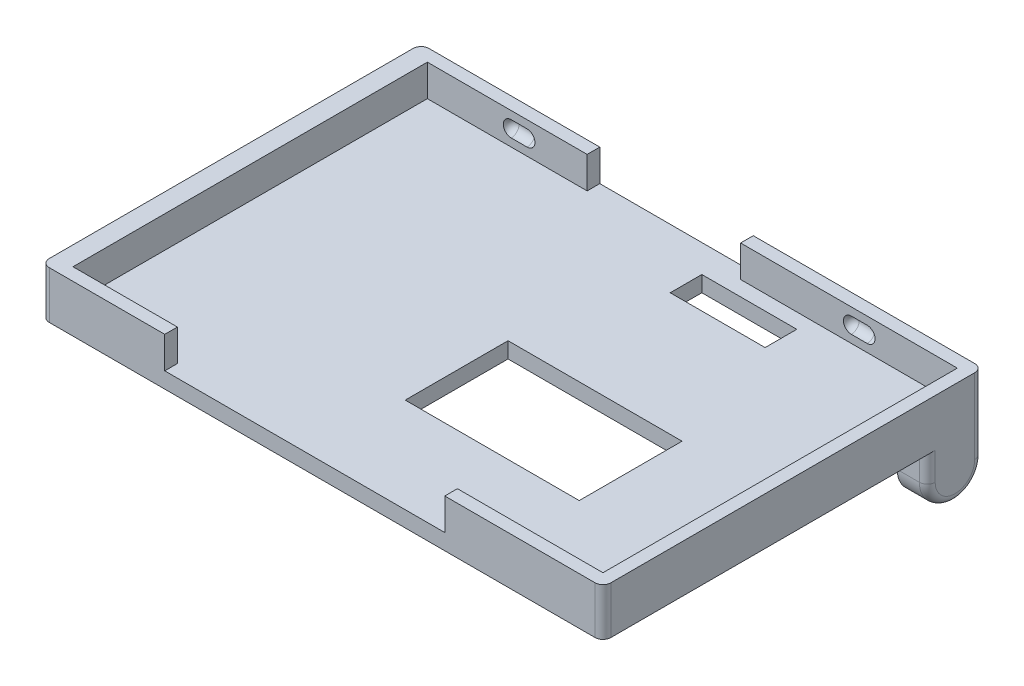
SolidWorks part; units mm, degrees
ref_plane "前视基准面" through (0, 0, 0) normal (0, 0, 1) x (1, 0, 0)
ref_plane "上视基准面" through (0, 0, 0) normal (0, 1, 0) x (1, 0, 0)
ref_plane "右视基准面" through (0, 0, 0) normal (1, 0, 0) x (0, 0, -1)
sketch "草图1" plane through (0, 0, 0) normal (0, 1, 0) x (1, 0, 0)
  line L1 (-17.75, 12) -> (17.75, 12)
  line L2 (-17.75, 12) -> (-17.75, -12)
  line L3 (-17.75, -12) -> (17.75, -12)
  line L4 (17.75, 12) -> (17.75, -12)
  line L5 (-17.75, 12) -> (17.75, -12) construction
  line L6 (-17.75, -12) -> (17.75, 12) construction
  point P0 (0, 0)
  dimension "D1" = 24
  dimension "D2" = 35.5
extrude "凸台-拉伸1" add sketch "草图1" along normal blind 3
sketch "草图2" plane through (0, 3, 0) normal (0, 1, 0) x (1, 0, 0)
  line L0 (17.75, 12) -> (-17.75, 12) construction
  line L1 (-15.75, 10) -> (15.75, 10)
  line L2 (-15.75, 10) -> (-15.75, -10)
  line L3 (-15.75, -10) -> (15.75, -10)
  line L4 (15.75, 10) -> (15.75, -10)
  line L5 (-15.75, 10) -> (15.75, -10) construction
  line L6 (-15.75, -10) -> (15.75, 10) construction
  line L7 (-17.75, 12) -> (-17.75, -12) construction
  point P0 (0, 0)
  dimension "D1" = 2
  dimension "D2" = 2
extrude "切除-拉伸1" cut sketch "草图2" against normal blind 2
sketch "草图4" plane through (0, 0, 0) normal (0, -1, 0) x (1, 0, 0)
  line L1 (-17.75, -12) -> (-15.85, -12)
  line L2 (-17.75, -12) -> (-17.75, -8.5)
  line L3 (-17.75, -8.5) -> (-15.85, -8.5)
  line L4 (-15.85, -12) -> (-15.85, -8.5)
  line L5 (17.75, -12) -> (15.85, -12)
  line L6 (17.75, -12) -> (17.75, -8.5)
  line L7 (17.75, -8.5) -> (15.85, -8.5)
  line L8 (15.85, -12) -> (15.85, -8.5)
  dimension "D1" = 3.5
  dimension "D2" = 1.9
  dimension "D3" = 1.9
  dimension "D4" = 3.5
extrude "凸台-拉伸2" add sketch "草图4" along normal blind 3.5
sketch "草图5" plane through (-17.75, 0, 0) normal (-1, 0, 0) x (0, 0, 1)
  line L1 (-12, 3) -> (-12, -3.5) construction
  line L2 (-12, -1.75) -> (-12, -3.5)
  line L5 (-10.25, -3.5) -> (-12, -3.5)
  arc A1 (-12, -1.75) -> (-10.25, -3.5) centre (-10.25, -1.75) ccw
  dimension "D1" = 1.75
extrude "切除-拉伸3" cut sketch "草图5" against normal blind 2
sketch "草图6" plane through (-17.75, 0, 0) normal (-1, 0, 0) x (0, 0, 1)
  line L0 (-8.5, -3.5) -> (-10.25, -3.5)
  line L1 (-8.5, -3.5) -> (-10.25, -3.5) construction
  line L2 (-8.5, -3.5) -> (-8.5, 0) construction
  line L3 (-8.5, -3.5) -> (-8.5, -1.75)
  arc A0 (-12, -1.75) -> (-10.25, -3.5) centre (-10.25, -1.75) ccw construction
  arc A1 (-10.25, -3.5) -> (-8.5, -1.75) centre (-10.25, -1.75) ccw
extrude "切除-拉伸4" cut sketch "草图6" against normal blind 2
sketch "草图7" plane through (17.75, 0, 0) normal (1, 0, 0) x (0, 0, -1)
  line L0 (8.5, -3.5) -> (10.25, -3.5)
  line L1 (12, -3.5) -> (8.5, -3.5) construction
  line L2 (8.5, -3.5) -> (8.5, 0) construction
  line L3 (8.5, -1.75) -> (8.5, -3.5)
  arc A0 (10.25, -3.5) -> (8.5, -1.75) centre (10.25, -1.75) cw
extrude "切除-拉伸5" cut sketch "草图7" against normal blind 2
sketch "草图8" plane through (17.75, 0, 0) normal (1, 0, 0) x (0, 0, -1)
  line L0 (12, -3.5) -> (10.25, -3.5)
  line L1 (12, 3) -> (12, -3.5) construction
  line L2 (12, -1.75) -> (12, -3.5)
  arc A0 (10.25, -3.5) -> (12, -1.75) centre (10.25, -1.75) ccw
extrude "切除-拉伸6" cut sketch "草图8" against normal blind 2
sketch "草图10" plane through (15.85, 0, 0) normal (-1, 0, 0) x (0, 0, 1)
  line L0 (-8.5, -1.75) -> (-8.5, 0) construction
  line L1 (12, 0) -> (-8.5, 0) construction
  circle A0 centre (-10.25, -1.75) radius 0.6
  dimension "D1" = 1.2
  dimension "D2" = 1.75
  dimension "D3" = 1.75
extrude "切除-拉伸8" cut sketch "草图10" against normal blind 1.5
sketch "草图11" plane through (0, 0, 0) normal (0, -1, 0) x (1, 0, 0)
  line L0 (17.75, 12) -> (17.75, -8.5) construction
  line L1 (1.75, -8.25) -> (7.75, -8.25)
  line L2 (1.75, -8.25) -> (1.75, -10.25)
  line L3 (1.75, -10.25) -> (7.75, -10.25)
  line L4 (7.75, -8.25) -> (7.75, -10.25)
  line L6 (15.85, -12) -> (-15.85, -12) construction
  dimension "D1" = 10
  dimension "D2" = 6
  dimension "D3" = 2
  dimension "D4" = 1.75
extrude "切除-拉伸9" cut sketch "草图11" against normal blind 2
sketch "草图12" plane through (-15.85, 0, 0) normal (1, 0, 0) x (0, 0, -1)
  line L0 (12, -1.75) -> (12, 0) construction
  line L1 (12, 0) -> (8.5, 0) construction
  circle A0 centre (10.25, -1.75) radius 0.6
  dimension "D1" = 1.2
  dimension "D2" = 1.75
  dimension "D3" = 1.75
extrude "切除-拉伸10" cut sketch "草图12" against normal blind 1.5
sketch "草图13" plane through (0, 3, 0) normal (0, 1, 0) x (1, 0, 0)
  line L1 (-15.6782, 11.2) -> (16.95, 11.2)
  line L2 (16.95, 11.2) -> (16.95, -11.2)
  line L3 (16.95, -11.2) -> (-15.75, -11.2)
  line L7 (17.75, 12) -> (-17.75, 12) construction
  line L10 (17.75, -12) -> (17.75, 12) construction
  line L11 (-17.75, -12) -> (17.75, -12) construction
  line L12 (-15.6782, 11.2) -> (-16.55, 11.2)
  line L13 (-16.55, 11.2) -> (-16.55, -11.2)
  line L14 (-16.55, -11.2) -> (-15.75, -11.2)
  line L15 (-17.75, 12) -> (-17.75, -12) construction
  dimension "D1" = 1.2
  dimension "D2" = 0.8
  dimension "D3" = 0.8
  dimension "D4" = 0.8
extrude "切除-拉伸11" cut sketch "草图13" against normal blind 2
sketch "草图14" plane through (0, 0, -11.2) normal (0, 0, 1) x (1, 0, 0)
  line L0 (16.95, 3) -> (-16.55, 3) construction
  line L1 (-11.25, 2.5) -> (-10.25, 2.5)
  line L2 (10.25, 2.5) -> (11.25, 2.5)
  line L3 (-11.75, 2) -> (-9.75, 2)
  line L4 (17.75, 3) -> (17.75, -1.75) construction
  line L5 (9.75, 2) -> (11.75, 2)
  line L6 (-17.75, 3) -> (-17.75, -1.75) construction
  arc A0 (-11.25, 2.5) -> (-11.75, 2) centre (-11.25, 2) ccw
  arc A2 (-10.25, 2.5) -> (-9.75, 2) centre (-10.25, 2) cw
  arc A4 (10.25, 2.5) -> (9.75, 2) centre (10.25, 2) ccw
  arc A5 (11.25, 2.5) -> (11.75, 2) centre (11.25, 2) cw
  point P4 (-10.75, 2.5)
  point P5 (-10.75, 2)
  point P14 (10.75, 2.5)
  point P15 (10.75, 2)
  dimension "D1" = 1
  dimension "D4" = 2
  dimension "D7" = 1
  dimension "D6" = 1
  dimension "D2" = 2
  dimension "D3" = 0.5
  dimension "D5" = 1
  dimension "D8" = 0.5
  dimension "D9" = 6
  dimension "D10" = 6
revolve "切除-旋转1" cut sketch "草图14" angle 360 about L5
sketch "草图15" plane through (0, 0, 11.2) normal (0, 0, -1) x (-1, 0, 0)
  line L0 (10.75, 2) -> (12.75, 2)
  line L1 (16.55, 1) -> (-16.95, 1) construction
  line L3 (-12.75, 2) -> (-10.75, 2)
  line L4 (-12.25, 2.5) -> (-11.25, 2.5)
  line L7 (-17.75, 3) -> (-17.75, 0) construction
  line L8 (11.25, 2.5) -> (12.25, 2.5)
  line L10 (17.75, 3) -> (17.75, 0) construction
  arc A4 (-12.25, 2.5) -> (-12.75, 2) centre (-12.25, 2) ccw
  arc A5 (-11.25, 2.5) -> (-10.75, 2) centre (-11.25, 2) cw
  arc A6 (11.25, 2.5) -> (10.75, 2) centre (11.25, 2) ccw
  arc A7 (12.25, 2.5) -> (12.75, 2) centre (12.25, 2) cw
  point P6 (-11.75, 2.5)
  point P9 (-11.75, 2)
  point P16 (11.75, 2.5)
  point P17 (11.75, 2)
  dimension "D1" = 2
  dimension "D2" = 1
  dimension "D6" = 5
  dimension "D3" = 1
  dimension "D4" = 0.5
  dimension "D5" = 2
  dimension "D7" = 1
  dimension "D8" = 5
revolve "切除-旋转2" cut sketch "草图15" angle 360 about L3
sketch "草图17" plane through (0, 3, 0) normal (0, 1, 0) x (1, 0, 0)
  line L0 (17.75, 12) -> (-17.75, 12) construction
  line L1 (16.95, 11.2) -> (-16.55, 11.2) construction
  line L2 (-6.45, 12) -> (3.25, 12)
  line L3 (-6.45, 12) -> (-6.45, 11.2)
  line L4 (-6.45, 11.2) -> (3.25, 11.2)
  line L5 (3.25, 12) -> (3.25, 11.2)
  line L6 (-17.75, 12) -> (-17.75, -12) construction
  line L7 (17.75, -12) -> (17.75, 12) construction
  dimension "D1" = 11.3
  dimension "D2" = 14.5
extrude "切除-拉伸12" cut sketch "草图17" against normal blind 2
sketch "草图18" plane through (0, 3, 0) normal (0, 1, 0) x (1, 0, 0)
  line L0 (-16.55, -11.2) -> (16.95, -11.2) construction
  line L1 (-9.95, -11.2) -> (7.75, -11.2)
  line L2 (-9.95, -11.2) -> (-9.95, -12)
  line L3 (-9.95, -12) -> (7.75, -12)
  line L4 (7.75, -11.2) -> (7.75, -12)
  line L5 (-17.75, -12) -> (17.75, -12) construction
  line L6 (-17.75, 12) -> (-17.75, -12) construction
  line L7 (17.75, -12) -> (17.75, 12) construction
  dimension "D1" = 7.8
  dimension "D2" = 10
extrude "切除-拉伸13" cut sketch "草图18" against normal blind 2
sketch "草图19" plane through (0, 0, 0) normal (0, -1, 0) x (1, 0, 0)
  line L0 (17.75, 12) -> (17.75, -8.5) construction
  line L1 (-0.75, 6) -> (10.25, 6)
  line L2 (-0.75, 6) -> (-0.75, -0.5)
  line L3 (-0.75, -0.5) -> (10.25, -0.5)
  line L4 (10.25, 6) -> (10.25, -0.5)
  line L5 (-17.75, 12) -> (17.75, 12) construction
  dimension "D1" = 6.5
  dimension "D2" = 11
  dimension "D3" = 7.5
  dimension "D4" = 6
extrude "切除-拉伸14" cut sketch "草图19" against normal blind 1
fillet "圆角1" radius 0.5 8 edges at (17.75, -0.875, -8.5) (17.75, -3.5, -10.25) (-17.75, -0.875, -8.5) (-17.75, -3.5, -10.25) (17.75, 1.5, 12) (17.75, 0.625, -12) (-17.75, 0.625, -12) (-17.75, 1.5, 12)
sketch "草图22" plane through (-15.85, 0, 0) normal (1, 0, 0) x (0, 0, -1)
  circle A1 centre (10.25, -1.75) radius 1.5
  dimension "D1" = 3
extrude "凸台-拉伸10" add sketch "草图22" along normal blind 0.2
sketch "草图23" plane through (-15.65, 0, 0) normal (1, 0, 0) x (0, 0, -1)
  circle A0 centre (10.25, -1.75) radius 0.6
  dimension "D1" = 1.2
extrude "切除-拉伸15" cut sketch "草图23" against normal blind 0.2
sketch "草图24" plane through (-15.65, 0, 0) normal (1, 0, 0) x (0, 0, -1)
  line L0 (10.25, -2.35) -> (10.25, -3.25)
  line L1 (10.0204, -2.3043) -> (9.676, -3.1358)
  line L2 (9.8257, -2.1743) -> (9.1893, -2.8107)
  line L3 (9.6957, -1.9796) -> (8.8642, -2.324)
  line L4 (9.65, -1.75) -> (8.75, -1.75)
  line L5 (9.6957, -1.5204) -> (8.8642, -1.176)
  line L6 (9.8257, -1.3257) -> (9.1893, -0.6893)
  line L7 (10.0204, -1.1957) -> (9.676, -0.3642)
  line L8 (10.25, -1.15) -> (10.25, -0.25)
  line L9 (10.4796, -1.1957) -> (10.824, -0.3642)
  line L10 (10.6743, -1.3257) -> (11.3107, -0.6893)
  line L11 (10.8043, -1.5204) -> (11.6358, -1.176)
  line L12 (10.85, -1.75) -> (11.75, -1.75)
  line L13 (10.8043, -1.9796) -> (11.6358, -2.324)
  line L14 (10.6743, -2.1743) -> (11.3107, -2.8107)
  line L15 (10.4796, -2.3043) -> (10.824, -3.1358)
  circle A0 centre (10.25, -1.75) radius 0.6 construction
  circle A1 centre (10.25, -1.75) radius 0.6 construction
  circle A2 centre (10.25, -1.75) radius 1.5 construction
  arc A3 (9.676, -3.1358) -> (10.25, -3.25) centre (10.25, -1.75) ccw
  arc A4 (10.824, -3.1358) -> (11.3107, -2.8107) centre (10.25, -1.75) ccw
  arc A5 (11.75, -1.75) -> (11.6358, -2.324) centre (10.25, -1.75) cw
  arc A6 (11.3107, -0.6893) -> (11.6358, -1.176) centre (10.25, -1.75) cw
  arc A7 (10.25, -0.25) -> (10.824, -0.3642) centre (10.25, -1.75) cw
  arc A8 (9.676, -0.3642) -> (9.1893, -0.6893) centre (10.25, -1.75) ccw
  arc A9 (8.8642, -1.176) -> (8.75, -1.75) centre (10.25, -1.75) ccw
  arc A10 (8.8642, -2.324) -> (9.1893, -2.8107) centre (10.25, -1.75) ccw
  arc A11 (9.6957, -1.9796) -> (9.8257, -2.1743) centre (10.25, -1.75) ccw
  arc A12 (10.0204, -2.3043) -> (10.25, -2.35) centre (10.25, -1.75) ccw
  arc A13 (10.4796, -2.3043) -> (10.6743, -2.1743) centre (10.25, -1.75) ccw
  arc A14 (10.8043, -1.9796) -> (10.85, -1.75) centre (10.25, -1.75) ccw
  arc A15 (10.8043, -1.5204) -> (10.6743, -1.3257) centre (10.25, -1.75) ccw
  arc A16 (10.4796, -1.1957) -> (10.25, -1.15) centre (10.25, -1.75) ccw
  arc A17 (10.0204, -1.1957) -> (9.8257, -1.3257) centre (10.25, -1.75) ccw
  arc A18 (9.6957, -1.5204) -> (9.65, -1.75) centre (10.25, -1.75) ccw
  point P42 (10.25, -1.75)
  dimension "D1" = 16
extrude "切除-拉伸16" cut sketch "草图24" against normal blind 0.2
fillet "圆角2" radius 0.1 16 edges at (-15.65, -2.1518, -9.2799) (-15.65, -1.75, -9.2) (-15.65, -1.3482, -9.2799) (-15.65, -1.0075, -9.5075) (-15.65, -0.7799, -9.8482) (-15.65, -0.7, -10.25) (-15.65, -0.7799, -10.6518) (-15.65, -1.0075, -10.9925) (-15.65, -1.3482, -11.2201) (-15.65, -1.75, -11.3) (-15.65, -2.1518, -11.2201) (-15.65, -2.4925, -10.9925) (-15.65, -2.7201, -10.6518) (-15.65, -2.8, -10.25) (-15.65, -2.4925, -9.5075) (-15.65, -2.7201, -9.8482)
sketch "草图25" plane through (15.85, 0, 0) normal (-1, 0, 0) x (0, 0, 1)
  circle A0 centre (-10.25, -1.75) radius 1.5
  dimension "D1" = 3
extrude "凸台-拉伸11" add sketch "草图25" along normal blind 0.2
sketch "草图26" plane through (15.65, 0, 0) normal (-1, 0, 0) x (0, 0, 1)
  circle A0 centre (-10.25, -1.75) radius 0.6
  dimension "D1" = 1.2
extrude "切除-拉伸17" cut sketch "草图26" against normal blind 0.2
sketch "草图27" plane through (15.65, 0, 0) normal (-1, 0, 0) x (0, 0, 1)
  line L0 (-10.25, -2.35) -> (-10.25, -3.25)
  line L1 (-10.4796, -2.3043) -> (-10.824, -3.1358)
  line L2 (-10.6743, -2.1743) -> (-11.3107, -2.8107)
  line L3 (-10.8043, -1.9796) -> (-11.6358, -2.324)
  line L4 (-10.85, -1.75) -> (-11.75, -1.75)
  line L5 (-10.8043, -1.5204) -> (-11.6358, -1.176)
  line L6 (-10.6743, -1.3257) -> (-11.3107, -0.6893)
  line L7 (-10.4796, -1.1957) -> (-10.824, -0.3642)
  line L8 (-10.25, -1.15) -> (-10.25, -0.25)
  line L9 (-10.0204, -1.1957) -> (-9.676, -0.3642)
  line L10 (-9.8257, -1.3257) -> (-9.1893, -0.6893)
  line L11 (-9.6957, -1.5204) -> (-8.8642, -1.176)
  line L12 (-9.65, -1.75) -> (-8.75, -1.75)
  line L13 (-9.6957, -1.9796) -> (-8.8642, -2.324)
  line L14 (-9.8257, -2.1743) -> (-9.1893, -2.8107)
  line L15 (-10.0204, -2.3043) -> (-9.676, -3.1358)
  circle A0 centre (-10.25, -1.75) radius 0.6 construction
  circle A1 centre (-10.25, -1.75) radius 1.5 construction
  arc A2 (-10.25, -0.25) -> (-10.824, -0.3642) centre (-10.25, -1.75) ccw
  arc A3 (-11.3107, -0.6893) -> (-11.6358, -1.176) centre (-10.25, -1.75) ccw
  arc A4 (-11.75, -1.75) -> (-11.6358, -2.324) centre (-10.25, -1.75) ccw
  arc A5 (-11.3107, -2.8107) -> (-10.824, -3.1358) centre (-10.25, -1.75) ccw
  arc A6 (-10.25, -3.25) -> (-9.676, -3.1358) centre (-10.25, -1.75) ccw
  arc A7 (-9.1893, -2.8107) -> (-8.8642, -2.324) centre (-10.25, -1.75) ccw
  arc A8 (-8.75, -1.75) -> (-8.8642, -1.176) centre (-10.25, -1.75) ccw
  arc A9 (-9.1893, -0.6893) -> (-9.676, -0.3642) centre (-10.25, -1.75) ccw
  arc A10 (-10.25, -1.15) -> (-10.4796, -1.1957) centre (-10.25, -1.75) ccw
  arc A11 (-10.6743, -1.3257) -> (-10.8043, -1.5204) centre (-10.25, -1.75) ccw
  arc A12 (-10.85, -1.75) -> (-10.8043, -1.9796) centre (-10.25, -1.75) ccw
  arc A13 (-10.6743, -2.1743) -> (-10.4796, -2.3043) centre (-10.25, -1.75) ccw
  arc A14 (-10.25, -2.35) -> (-10.0204, -2.3043) centre (-10.25, -1.75) ccw
  arc A15 (-9.8257, -2.1743) -> (-9.6957, -1.9796) centre (-10.25, -1.75) ccw
  arc A16 (-9.65, -1.75) -> (-9.6957, -1.5204) centre (-10.25, -1.75) ccw
  arc A17 (-9.8257, -1.3257) -> (-10.0204, -1.1957) centre (-10.25, -1.75) ccw
  point P40 (-10.25, -1.75)
  dimension "D1" = 16
extrude "切除-拉伸19" cut sketch "草图27" against normal blind 0.2
fillet "圆角3" radius 0.1 16 edges at (15.65, -1.0075, -9.5075) (15.65, -1.3482, -9.2799) (15.65, -1.75, -9.2) (15.65, -2.1518, -9.2799) (15.65, -2.4925, -9.5075) (15.65, -2.7201, -9.8482) (15.65, -2.8, -10.25) (15.65, -2.7201, -10.6518) (15.65, -2.4925, -10.9925) (15.65, -2.1518, -11.2201) (15.65, -1.75, -11.3) (15.65, -1.3482, -11.2201) (15.65, -1.0075, -10.9925) (15.65, -0.7799, -10.6518) (15.65, -0.7, -10.25) (15.65, -0.7799, -9.8482)
